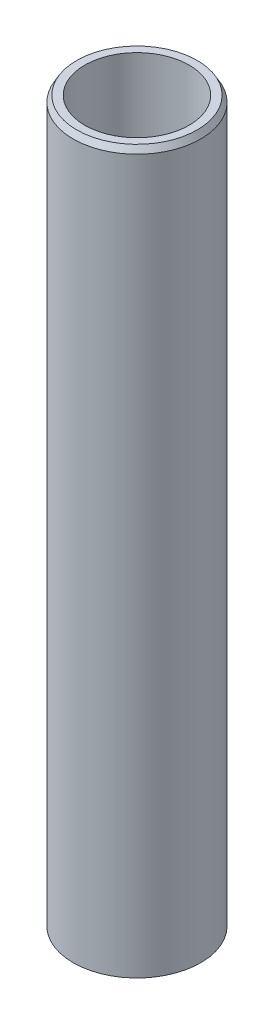
SolidWorks part; units mm, degrees
ref_plane "Front Plane" through (0, 0, 0) normal (0, 0, 1) x (1, 0, 0)
ref_plane "Top Plane" through (0, 0, 0) normal (0, 1, 0) x (1, 0, 0)
ref_plane "Right Plane" through (0, 0, 0) normal (1, 0, 0) x (0, 0, -1)
sketch "Sketch1" plane through (0, 0, 0) normal (0, 1, 0) x (1, 0, 0)
  circle A0 centre (0, 0) radius 30
  dimension "SHAFT_OD" = 60
extrude "Boss-Extrude1" add sketch "Sketch1" along normal blind 340.2472
sketch "Sketch2" plane through (0, 0, 0) normal (0, 1, 0) x (1, 0, 0)
  circle A0 centre (0, 0) radius 24.5488
  dimension "BORE_D" = 49.0976
extrude "Cut-Extrude1" cut sketch "Sketch2" along normal through all
chamfer "Chamfer1" distance 2.8722 angle 30 2 edges at (0, 340.2472, 30) (0, 0, 30) first distance on face at (0, 340.2472, 30) first distance on face at (0, 0, 24.5488)
